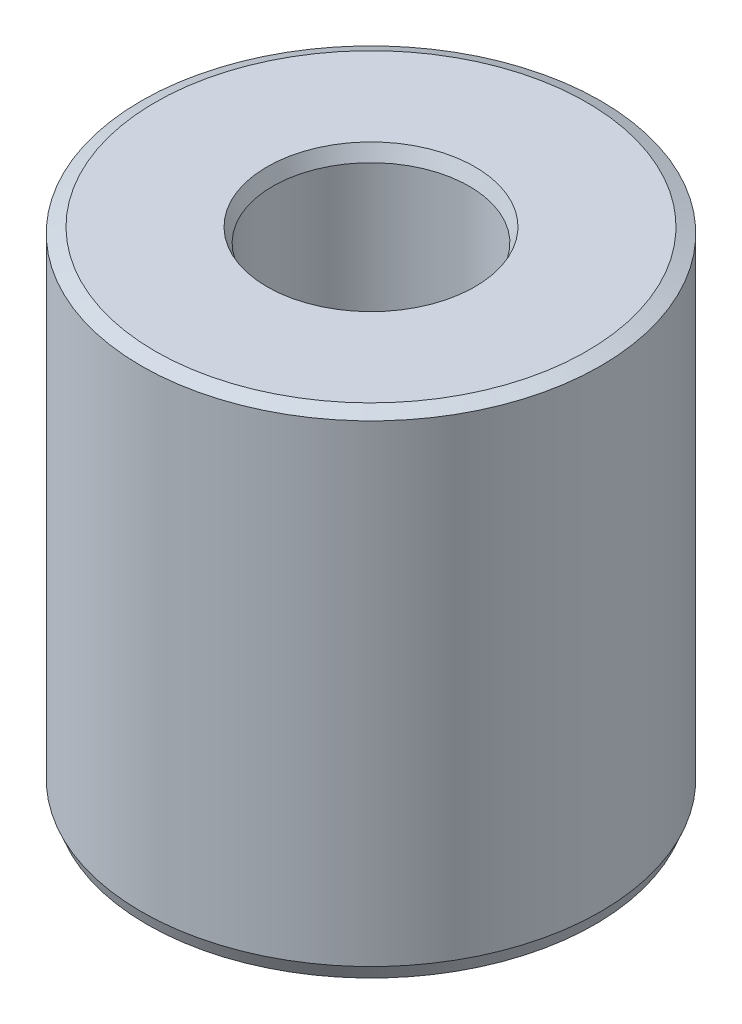
SolidWorks part; units mm, degrees
ref_plane "Front Plane" through (0, 0, 0) normal (0, 0, 1) x (1, 0, 0)
ref_plane "Top Plane" through (0, 0, 0) normal (0, 1, 0) x (1, 0, 0)
ref_plane "Right Plane" through (0, 0, 0) normal (1, 0, 0) x (0, 0, -1)
sketch "Sketch1" plane through (0, 0, 0) normal (0, 1, 0) x (1, 0, 0)
  circle A0 centre (0, 0) radius 17.5
  dimension "SLEEVE_OD" = 35
extrude "Boss-Extrude1" add sketch "Sketch1" along normal blind 37.5116
sketch "Sketch2" plane through (0, 0, 0) normal (0, 1, 0) x (1, 0, 0)
  circle A0 centre (0, 0) radius 7.4865
  dimension "BORE_D" = 14.973
extrude "Cut-Extrude1" cut sketch "Sketch2" along normal through all
chamfer "Chamfer1" distance 0.4354 angle 67.753 4 edges at (0, 37.5116, 7.4865) (0, 0, 7.4865) (0, 0, 17.5) (0, 37.5116, 17.5) first distance on face at (0, 37.5116, 7.4865) first distance on face at (0, 0, 7.4865) first distance on face at (0, 37.5116, 17.5)
